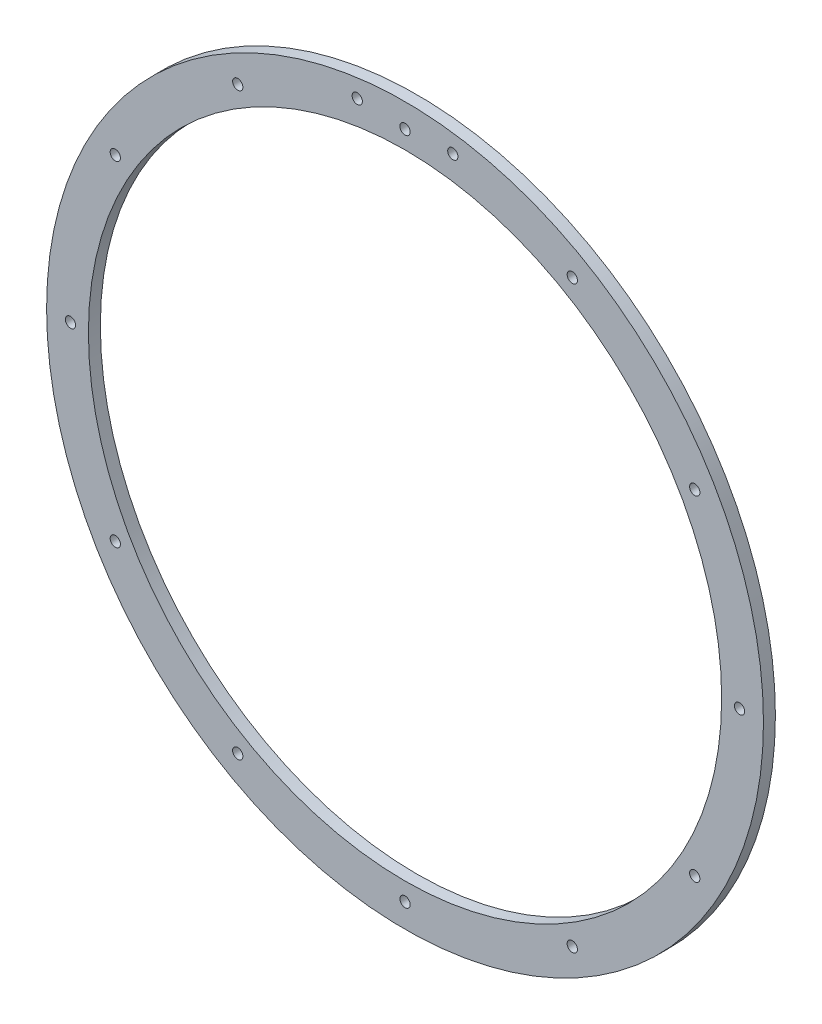
SolidWorks part; units mm, degrees
material "A-玻璃纤维"
ref_plane "前视基准面" through (0, 0, 0) normal (0, 0, 1) x (1, 0, 0)
ref_plane "上视基准面" through (0, 0, 0) normal (0, 1, 0) x (1, 0, 0)
ref_plane "右视基准面" through (0, 0, 0) normal (1, 0, 0) x (0, 0, -1)
sketch "草图1" plane through (0, 0, 0) normal (0, 0, 1) x (1, 0, 0)
  line L6 (-170, 50) -> (-170, -50)
  line L7 (-160, -60) -> (-143.8749, -60)
  line L8 (143.8749, -60) -> (160, -60)
  line L9 (170, -50) -> (170, 50)
  line L10 (160, 60) -> (143.8749, 60)
  line L11 (-143.8749, 60) -> (-160, 60)
  line L12 (-170, 50) -> (-170, -50)
  line L13 (-160, -60) -> (-143.8749, -60)
  line L14 (143.8749, -60) -> (160, -60)
  line L15 (170, -50) -> (170, 50)
  line L16 (160, 60) -> (143.8749, 60)
  line L17 (-143.8749, 60) -> (-160, 60)
  arc A1 (0, -132.5) -> (0, 132.5) centre (0, 0) ccw construction
  arc A2 (0, 132.5) -> (0, -132.5) centre (0, 0) ccw construction
  arc A3 (0, -132.5) -> (0, 132.5) centre (0, 0) ccw
  arc A4 (0, 132.5) -> (0, -132.5) centre (0, 0) ccw
  arc A11 (-170, -50) -> (-160, -60) centre (-160, -50) ccw
  arc A12 (-134.8828, -65.625) -> (-143.8749, -60) centre (-143.8749, -70) ccw
  arc A13 (-134.8828, -65.625) -> (0, -150) centre (0, 0) ccw
  arc A14 (0, -150) -> (134.8828, -65.625) centre (0, 0) ccw
  arc A15 (143.8749, -60) -> (134.8828, -65.625) centre (143.8749, -70) ccw
  arc A16 (160, -60) -> (170, -50) centre (160, -50) ccw
  arc A17 (170, 50) -> (160, 60) centre (160, 50) ccw
  arc A18 (134.8828, 65.625) -> (143.8749, 60) centre (143.8749, 70) ccw
  arc A19 (134.8828, 65.625) -> (-134.8828, 65.625) centre (0, 0) ccw
  arc A20 (-143.8749, 60) -> (-134.8828, 65.625) centre (-143.8749, 70) ccw
  arc A21 (-160, 60) -> (-170, 50) centre (-160, 50) ccw
  arc A22 (-170, -50) -> (-160, -60) centre (-160, -50) ccw
  arc A23 (-134.8828, -65.625) -> (-143.8749, -60) centre (-143.8749, -70) ccw
  arc A24 (-134.8828, -65.625) -> (0, -150) centre (0, 0) ccw
  arc A25 (0, -150) -> (134.8828, -65.625) centre (0, 0) ccw
  arc A26 (143.8749, -60) -> (134.8828, -65.625) centre (143.8749, -70) ccw
  arc A27 (160, -60) -> (170, -50) centre (160, -50) ccw
  arc A28 (170, 50) -> (160, 60) centre (160, 50) ccw
  arc A29 (134.8828, 65.625) -> (143.8749, 60) centre (143.8749, 70) ccw
  arc A30 (134.8828, 65.625) -> (-134.8828, 65.625) centre (0, 0) ccw
  arc A31 (-143.8749, 60) -> (-134.8828, 65.625) centre (-143.8749, 70) ccw
  arc A32 (-160, 60) -> (-170, 50) centre (-160, 50) ccw
  dimension "D1" = 0
extrude "凸台-拉伸2" add sketch "草图1" along normal blind 5
sketch "草图2" plane through (0, 0, 5) normal (0, 0, 1) x (1, 0, 0)
  circle A0 centre (0, 0) radius 150
  circle A1 centre (0, 0) radius 183.3052
extrude "切除-拉伸1" cut sketch "草图2" against normal blind 10
sketch "草图3" plane through (0, 0, 5) normal (0, 0, 1) x (1, 0, 0)
  circle A0 centre (0, 0) radius 140 construction
  circle A2 centre (0, 140) radius 2.15
  circle A3 centre (70, 121.2436) radius 2.15
  circle A4 centre (121.2436, 70) radius 2.15
  circle A5 centre (140, 0) radius 2.15
  circle A6 centre (121.2436, -70) radius 2.15
  circle A7 centre (70, -121.2436) radius 2.15
  circle A8 centre (0, -140) radius 2.15
  circle A9 centre (-70, -121.2436) radius 2.15
  circle A10 centre (-121.2436, -70) radius 2.15
  circle A11 centre (-140, 0) radius 2.15
  circle A12 centre (-121.2436, 70) radius 2.15
  circle A13 centre (-70, 121.2436) radius 2.15
  point P29 (0, 0)
  dimension "D1" = 280
  dimension "D4" = 4.3
  dimension "D2" = 12
extrude "切除-拉伸2" cut sketch "草图3" against normal blind 10
sketch "草图4" plane through (0, 0, 5) normal (0, 0, 1) x (1, 0, 0)
  circle A0 centre (0, 0) radius 142.5 construction
  circle A1 centre (-20, 141.0895) radius 2.15
  circle A2 centre (20, 141.0895) radius 2.15
  dimension "D1" = 285
  dimension "D4" = 4.3
  dimension "D5" = 4.3
  dimension "D2" = 40
  dimension "D3" = 20
extrude "切除-拉伸3" cut sketch "草图4" against normal blind 10
